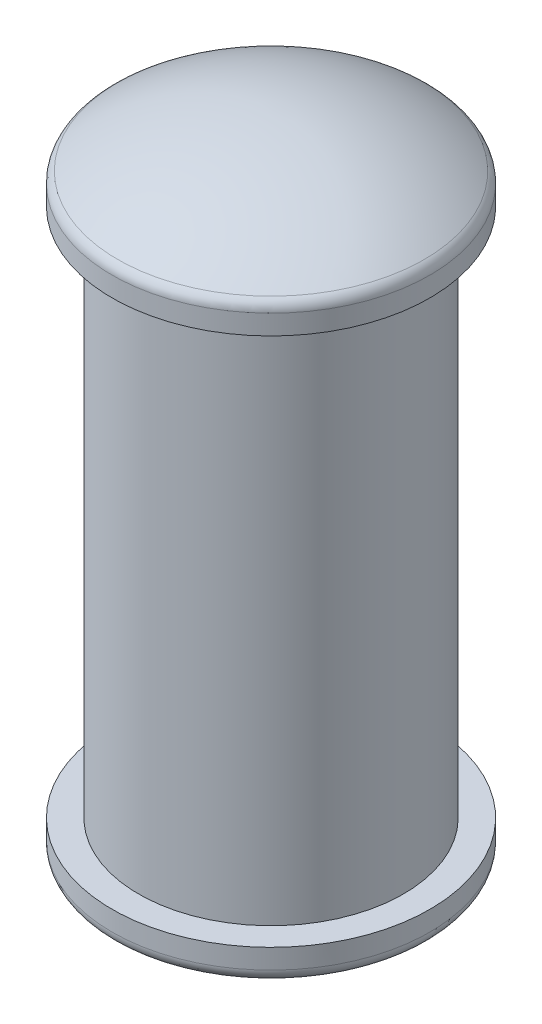
SolidWorks part; units mm, degrees
ref_plane "Front Plane" through (0, 0, 0) normal (0, 0, 1) x (1, 0, 0)
ref_plane "Top Plane" through (0, 0, 0) normal (0, 1, 0) x (1, 0, 0)
ref_plane "Right Plane" through (0, 0, 0) normal (1, 0, 0) x (0, 0, -1)
sketch "Sketch1" plane through (0, 0, 0) normal (0, 0, 1) x (1, 0, 0)
  line L0 (0, 0) -> (0, 5.5)
  line L1 (0, 5.5) -> (-3, 5.5)
  line L2 (-3, 5.5) -> (-3, 5)
  line L3 (-3, 5) -> (-2.5, 5)
  line L4 (-2.5, 5) -> (-2.5, 0)
  line L5 (-2.5, 0) -> (0, 0)
  dimension "D1" = 2.5
  dimension "D2" = 5
  dimension "D3" = 0.5
  dimension "D4" = 0.5
revolve "Revolve1" add sketch "Sketch1" angle 360 about L0
dome "Dome1" faces to dome 1 distance 1 reverse direction no elliptical dome no face at (0, 5.5, -3) parameters "D1"=1
mirror "Mirror1" about plane through (-2.5, 0, 0) normal (0, 1, 0) of "Dome1", "Revolve1"
fillet "Fillet1" radius 0.25 2 edges at (0, -5.5, -3) (0, 5.5, -3)
